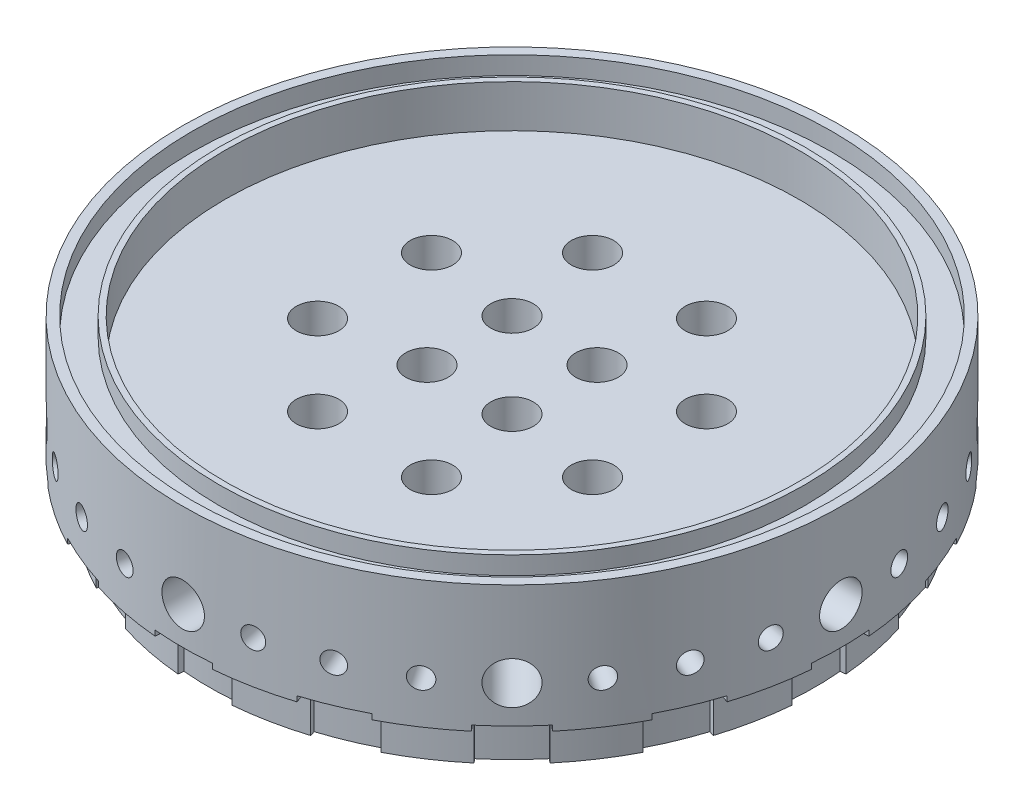
SolidWorks part; units mm, degrees
material "6061-T4 (SS)"
ref_plane "Front Plane" through (0, 0, 0) normal (0, 0, 1) x (1, 0, 0)
ref_plane "Top Plane" through (0, 0, 0) normal (0, 1, 0) x (1, 0, 0)
ref_plane "Right Plane" through (0, 0, 0) normal (1, 0, 0) x (0, 0, -1)
ref_axis "Axis1" through (0, -42.3, 0) along (0, 1, 0)
sketch "Sketch1" plane through (0, 0, 0) normal (0, 0, 1) x (1, 0, 0)
  line L0 (0, 0) -> (-46.0375, 0)
  line L5 (-46.0375, 0) -> (-46.0375, 6.35)
  line L6 (-46.0375, 6.35) -> (-49.2125, 6.35)
  line L7 (-49.2125, 6.35) -> (-49.2125, 25.4)
  line L10 (-42.8625, 19.05) -> (0, 19.05)
  line L11 (0, 19.05) -> (0, 0)
  line L12 (-42.8625, 19.05) -> (-42.8625, 25.4)
  line L15 (-49.2125, 25.4) -> (-47.7774, 25.4)
  line L16 (-47.7774, 25.4) -> (-47.7774, 22.7076)
  line L17 (-47.7774, 22.7076) -> (-43.7134, 22.7076)
  line L18 (-43.7134, 22.7076) -> (-43.7134, 25.4)
  line L19 (-43.7134, 25.4) -> (-42.8625, 25.4)
  point P4 (-46.3091, 5.5562)
  point P5 (-46.0375, 0.2183)
  dimension "D1" = 46.0375
  dimension "D3" = 19.05
  dimension "D6" = 3.175
  dimension "D7" = 6.35
  dimension "D9" = 19.05
  dimension "D10" = 4.064
  dimension "D11" = 2.6924
  dimension "D12" = 6.35
  dimension "o-ring -238" = 47.7774
revolve "Revolve1" add sketch "Sketch1" angle 360 about L11
ref_plane "Plane1" through (49.2125, 0, 0) normal (1, 0, 0) x (0, 0, -1)
hole_wizard "1/8 (0.125) Diameter Hole2" positions "Sketch36" profile "Sketch37" hole size "1/8" standard "ANSI Inch"
sketch "Sketch36" plane through (49.2125, 0, 0) normal (1, 0, 0) x (0, 0, -1)
  line L0 (0, 13.97) -> (0, -13.97) construction
  point P0 (0, 12.7)
  dimension "D1" = 12.7
sketch "Sketch37" plane through (49.2125, 12.7, 0) normal (0, 1, 0) x (0, 0, -1)
  line L0 (0, 0) -> (0, 13.6539)
  line L1 (0, 13.6539) -> (1.5875, 12.7)
  line L2 (1.5875, 12.7) -> (1.5875, 0)
  line L5 (1.5875, 0) -> (0, 0)
  line L10 (0, 13.6539) -> (-1.5875, 12.7) construction
  line L11 (0, -6.35) -> (0, 107.95) construction
  dimension "Hole Dia." = 3.175
  dimension "Hole Depth" = 12.7
  dimension "Drill Angle" = 118
pattern_circular "CirPattern9" count 32 over 360 about axis through (0, -42.3, 0) along (0, 1, 0) of "1/8 (0.125) Diameter Hole2"
hole_wizard "1/4 (0.25) Diameter Hole1" positions "Sketch12" profile "Sketch13" hole size "1/4" standard "ANSI Inch"
sketch "Sketch12" plane through (49.2125, 0, 0) normal (1, 0, 0) x (0, 0, -1)
  point P0 (0, 12.7)
  dimension "D1" = 12.7
sketch "Sketch13" plane through (49.2125, 12.7, 0) normal (0, 1, 0) x (0, 0, -1)
  line L0 (0, 0) -> (0, 14.6077)
  line L1 (0, 14.6077) -> (3.175, 12.7)
  line L2 (3.175, 12.7) -> (3.175, 0)
  line L5 (3.175, 0) -> (0, 0)
  line L10 (0, 14.6077) -> (-3.175, 12.7) construction
  line L11 (0, -6.35) -> (0, 107.95) construction
  dimension "Hole Dia." = 6.35
  dimension "Hole Depth" = 12.7
  dimension "Drill Angle" = 118
hole_wizard "3/16 (0.1875) Diameter Hole1" positions "Sketch14" profile "Sketch15" hole size "3/16" standard "ANSI Inch"
sketch "Sketch14" plane through (49.2125, 0, 0) normal (1, 0, 0) x (0, 0, -1)
  point P0 (0, 12.7)
sketch "Sketch15" plane through (49.2125, 12.7, 0) normal (0, 1, 0) x (0, 0, -1)
  line L0 (0, 0) -> (0, 33.1808)
  line L1 (0, 33.1808) -> (2.3812, 31.75)
  line L2 (2.3812, 31.75) -> (2.3812, 0)
  line L5 (2.3812, 0) -> (0, 0)
  line L10 (0, 33.1808) -> (-2.3813, 31.75) construction
  line L11 (0, -6.35) -> (0, 107.95) construction
  dimension "Hole Dia." = 4.7625
  dimension "Hole Depth" = 31.75
  dimension "Drill Angle" = 118
hole_wizard "1/8 (0.125) Diameter Hole1" positions "Sketch16" profile "Sketch17" hole size "1/8" standard "ANSI Inch"
sketch "Sketch16" plane through (49.2125, 0, 0) normal (1, 0, 0) x (0, 0, -1)
  point P0 (0, 12.7)
sketch "Sketch17" plane through (49.2125, 12.7, 0) normal (0, 1, 0) x (0, 0, -1)
  line L0 (0, 0) -> (0, 45.4039)
  line L1 (0, 45.4039) -> (1.5875, 44.45)
  line L2 (1.5875, 44.45) -> (1.5875, 0)
  line L5 (1.5875, 0) -> (0, 0)
  line L10 (0, 45.4039) -> (-1.5875, 44.45) construction
  line L11 (0, -6.35) -> (0, 107.95) construction
  dimension "Hole Dia." = 3.175
  dimension "Hole Depth" = 44.45
  dimension "Drill Angle" = 118
pattern_circular "CirPattern1" count 8 over 360 about axis through (0, -42.3, 0) along (0, 1, 0) of "1/4 (0.25) Diameter Hole1"
pattern_circular "CirPattern2" count 8 over 360 about axis through (0, -42.3, 0) along (0, 1, 0) of "3/16 (0.1875) Diameter Hole1"
pattern_circular "CirPattern3" count 4 over 360 about axis through (0, -42.3, 0) along (0, 1, 0) of "1/8 (0.125) Diameter Hole1"
ref_plane "Plane2" through (0, 19.05, 0) normal (0, 1, 0) x (1, 0, 0)
hole_wizard "inner large LOX holes" positions "Sketch19" profile "Sketch20" hole size "1/4" standard "ANSI Inch"
sketch "Sketch19" plane through (0, 19.05, 0) normal (0, 1, 0) x (1, 0, 0)
  line L2 (-6.35, 0) -> (0, 0) construction
  line L4 (-6.35, -6.35) -> (-6.35, 0) construction
  point P0 (-6.35, -6.35)
  dimension "D1" = 6.35
  dimension "D2" = 6.35
sketch "Sketch20" plane through (-6.35, 19.05, 6.35) normal (1, 0, 0) x (0, 0, 1)
  line L0 (0, 0) -> (0, 14.6077)
  line L1 (0, 14.6077) -> (3.175, 12.7)
  line L2 (3.175, 12.7) -> (3.175, 0)
  line L5 (3.175, 0) -> (0, 0)
  line L10 (0, 14.6077) -> (-3.175, 12.7) construction
  line L11 (0, -6.35) -> (0, 107.95) construction
  dimension "Hole Dia." = 6.35
  dimension "Hole Depth" = 12.7
  dimension "Drill Angle" = 118
hole_wizard "outer large LOX hole" positions "Sketch21" profile "Sketch22" hole size "1/4" standard "ANSI Inch"
sketch "Sketch21" plane through (0, 19.05, 0) normal (0, 1, 0) x (1, 0, 0)
  line L0 (-20.5332, -8.5051) -> (0, 0) construction
  line L2 (0, 0) -> (-17.5003, 0) construction
  point P0 (-20.5332, -8.5051)
  dimension "D1" = 22.5
  dimension "D2" = 22.225
sketch "Sketch22" plane through (-20.5332, 19.05, 8.5051) normal (1, 0, 0) x (0, 0, 1)
  line L0 (0, 0) -> (0, 14.6077)
  line L1 (0, 14.6077) -> (3.175, 12.7)
  line L2 (3.175, 12.7) -> (3.175, 0)
  line L5 (3.175, 0) -> (0, 0)
  line L10 (0, 14.6077) -> (-3.175, 12.7) construction
  line L11 (0, -6.35) -> (0, 107.95) construction
  dimension "Hole Dia." = 6.35
  dimension "Hole Depth" = 12.7
  dimension "Drill Angle" = 118
pattern_circular "CirPattern4" count 4 over 360 about axis through (0, -42.3, 0) along (0, 1, 0) of "inner large LOX holes"
pattern_circular "CirPattern5" count 8 over 360 about axis through (0, -42.3, 0) along (0, 1, 0) of "outer large LOX hole"
ref_plane "Plane4" through (-41.275, 0, 0) normal (1, 0, 0) x (0, 0, -1)
ref_axis "Axis4" through (-41.275, 0, -54.1338) along (0, 0, 1)
ref_plane "Plane5" through (-0.3135, -3.5837, 0) normal (0.0872, 0.9962, 0) x (0, 0, 1)
ref_plane "Plane6" through (-0.4519, -5.1651, 0) normal (0.0872, 0.9962, 0) x (0, 0, 1)
hole_wizard "1/16 (0.0625) Diameter Hole2" positions "Sketch27" profile "Sketch28" hole size "1/16" standard "ANSI Inch"
sketch "Sketch27" plane through (0, 0, 0) normal (0, 1, 0) x (1, 0, 0)
  point P0 (-6.35, 0)
  dimension "D1" = 6.35
sketch "Sketch28" plane through (-6.35, 0, 0) normal (1, 0, 0) x (0, 0, -1)
  line L0 (0, 0) -> (0, 13.1769)
  line L1 (0, 13.1769) -> (0.7937, 12.7)
  line L2 (0.7937, 12.7) -> (0.7937, 0)
  line L5 (0.7937, 0) -> (0, 0)
  line L10 (0, 13.1769) -> (-0.7938, 12.7) construction
  line L11 (0, -6.35) -> (0, 107.95) construction
  dimension "Hole Dia." = 1.5875
  dimension "Hole Depth" = 12.7
  dimension "Drill Angle" = 118
ref_axis "Axis2" through (0, 19.05, -88.99) along (0, 0, 1)
ref_axis "Axis3" through (2.4606, 19.05, 0) along (-1, 0, 0)
ref_plane "impinging plane" through (0, -6.35, 0) normal (0, -1, 0) x (-1, 0, 0)
ref_axis "Axis5" through (-53.7659, -6.35, 0) along (1, 0, 0)
ref_plane "Plane8" through (0, -4.7625, -2.7496) normal (0, -0.866, -0.5) x (1, 0, 0)
hole_wizard "1/16 (0.0625) Diameter Hole1" positions "Sketch31" profile "Sketch30" hole size "1/16" standard "ANSI Inch"
sketch "Sketch31" plane through (0, -4.7625, -2.7496) normal (0, -0.866, -0.5) x (1, 0, 0)
  line L0 (-53.7659, 3.175) -> (54.5016, 3.175) construction
  point P0 (-6.35, 3.175)
  dimension "D1" = 6.35
sketch "Sketch30" plane through (-6.35, -6.35, 0) normal (1, 0, 0) x (0, 0.5, -0.866)
  line L0 (0, 0) -> (0, 16.0979)
  line L1 (0, 16.0979) -> (0.7937, 15.621)
  line L2 (0.7937, 15.621) -> (0.7937, 0)
  line L5 (0.7937, 0) -> (0, 0)
  line L10 (0, 16.0979) -> (-0.7938, 15.621) construction
  line L11 (0, -6.35) -> (0, 107.95) construction
  dimension "Hole Dia." = 1.5875
  dimension "Hole Depth" = 15.621
  dimension "Drill Angle" = 118
hole_wizard "1/16 (0.0625) Diameter Hole3" positions "Sketch32" profile "Sketch33" hole size "1/16" standard "ANSI Inch"
sketch "Sketch32" plane through (0, 0, 0) normal (0, 1, 0) x (1, 0, 0)
  point P0 (-22.225, 0)
  dimension "D1" = 22.225
sketch "Sketch33" plane through (-22.225, 0, 0) normal (1, 0, 0) x (0, 0, -1)
  line L0 (0, 0) -> (0, 13.1769)
  line L1 (0, 13.1769) -> (0.7937, 12.7)
  line L2 (0.7937, 12.7) -> (0.7937, 0)
  line L5 (0.7937, 0) -> (0, 0)
  line L10 (0, 13.1769) -> (-0.7938, 12.7) construction
  line L11 (0, -6.35) -> (0, 107.95) construction
  dimension "Hole Dia." = 1.5875
  dimension "Hole Depth" = 12.7
  dimension "Drill Angle" = 118
hole_wizard "1/16 (0.0625) Diameter Hole4" positions "Sketch34" profile "Sketch35" hole size "1/16" standard "ANSI Inch"
sketch "Sketch34" plane through (0, -4.7625, -2.7496) normal (0, -0.866, -0.5) x (1, 0, 0)
  line L0 (-53.7659, 3.175) -> (54.5016, 3.175) construction
  point P0 (-22.225, 3.175)
  dimension "D1" = 22.225
sketch "Sketch35" plane through (-22.225, -6.35, 0) normal (1, 0, 0) x (0, 0.5, -0.866)
  line L0 (0, 0) -> (0, 19.5269)
  line L1 (0, 19.5269) -> (0.7937, 19.05)
  line L2 (0.7937, 19.05) -> (0.7937, 0)
  line L5 (0.7937, 0) -> (0, 0)
  line L10 (0, 19.5269) -> (-0.7938, 19.05) construction
  line L11 (0, -6.35) -> (0, 107.95) construction
  dimension "Hole Dia." = 1.5875
  dimension "Hole Depth" = 19.05
  dimension "Drill Angle" = 118
mirror "Mirror1" about plane through (0, 0, 0) normal (0, 0, 1) of "1/16 (0.0625) Diameter Hole1"
mirror "Mirror2" about plane through (0, 0, 0) normal (0, 0, 1) of "1/16 (0.0625) Diameter Hole4"
pattern_circular "CirPattern7" count 4 over 360 about axis through (0, -42.3, 0) along (0, 1, 0) of "1/16 (0.0625) Diameter Hole1", "Mirror1", "1/16 (0.0625) Diameter Hole2"
pattern_circular "CirPattern8" count 8 over 360 about axis through (0, -42.3, 0) along (0, 1, 0) of "Mirror2", "1/16 (0.0625) Diameter Hole4", "1/16 (0.0625) Diameter Hole3"
sketch "Sketch38" plane through (0, 6.35, 0) normal (0, -1, 0) x (1, 0, 0)
  line L0 (45.0716, -3.9433) -> (0, 0) construction
  line L1 (0, 0) -> (45.0716, 3.9433) construction
  line L2 (45.0716, -3.9433) -> (49.0252, -4.2892) construction
  line L3 (45.0716, 3.9433) -> (49.0252, 4.2892) construction
  line L4 (45.0716, -3.9433) -> (49.0252, -4.2892)
  line L5 (45.0716, 3.9433) -> (49.0252, 4.2892)
  circle A0 centre (0, 0) radius 45.2437 construction
  circle A1 centre (0, 0) radius 46.0375 construction
  arc A2 (45.0716, -3.9433) -> (45.0716, 3.9433) centre (0, 0) ccw
  arc A4 (49.0252, -4.2892) -> (49.0252, 4.2892) centre (0, 0) ccw
  circle A5 centre (0, 0) radius 49.2125 construction
  point P7 (0, 0)
  point P8 (45.2437, 0)
  point P11 (0, 0)
  point P13 (49.0252, 4.2892)
  point P16 (49.0252, -4.2892)
  dimension "D1" = 0.7937
  dimension "D2" = 10
extrude "Cut-Extrude1" cut sketch "Sketch38" along normal through all and the other way blind 0.7937
pattern_circular "CirPattern10" count 16 over 360 about axis through (0, 19.05, 0) along (0, 1, 0) of "Cut-Extrude1" reverse direction yes
